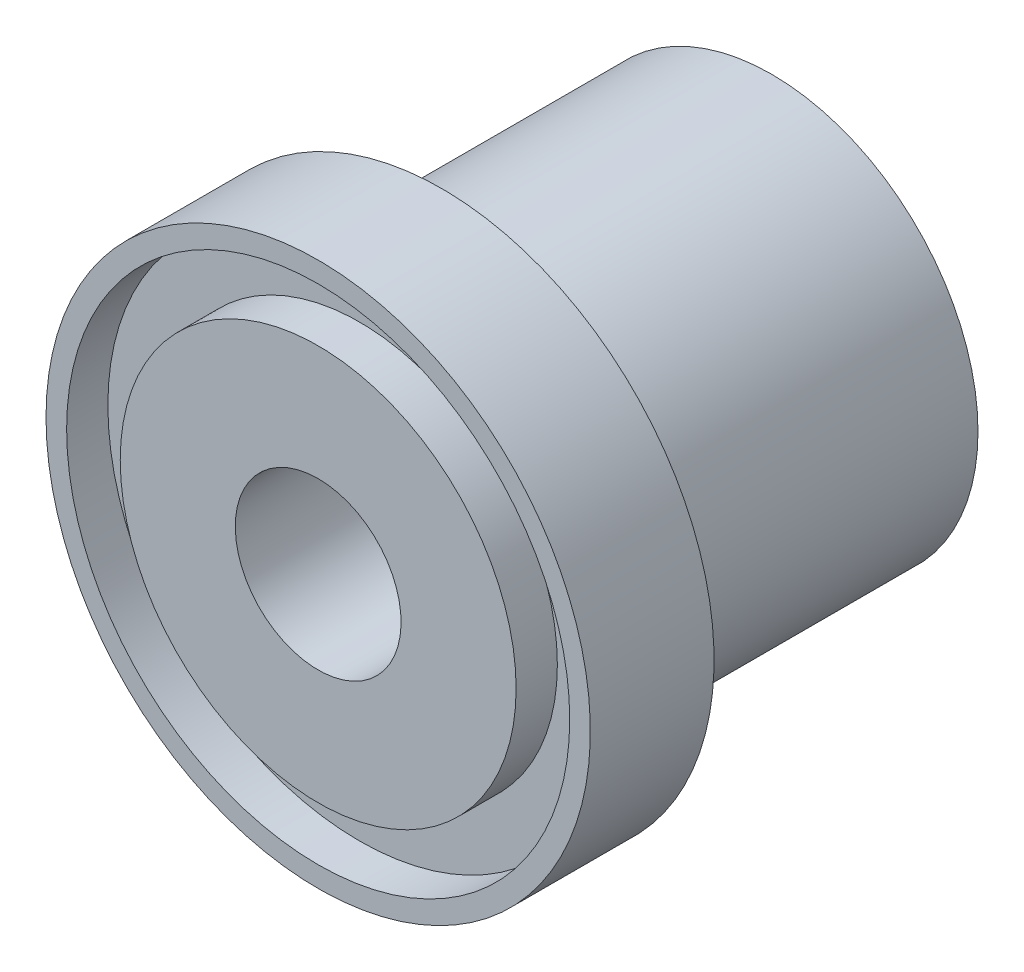
SolidWorks part; units mm, degrees
ref_plane "Front Plane" through (0, 0, 0) normal (0, 0, 1) x (1, 0, 0)
ref_plane "Top Plane" through (0, 0, 0) normal (0, 1, 0) x (1, 0, 0)
ref_plane "Right Plane" through (0, 0, 0) normal (1, 0, 0) x (0, 0, -1)
sketch "Sketch1" plane through (0, 0, 0) normal (0, 0, 1) x (1, 0, 0)
  circle A0 centre (43.1743, 8.5503) radius 6.35
  dimension "D2" = 12.7
extrude "Boss-Extrude1" add sketch "Sketch1" against normal up to surface (10.16 mm away)
sketch "Sketch3" plane through (0, 0, 0) normal (0, 0, 1) x (1, 0, 0)
  circle A0 centre (43.1743, 8.5503) radius 8.382
  dimension "D1" = 16.764
extrude "Boss-Extrude2" add sketch "Sketch3" along normal blind 3.81
sketch "Sketch5" plane through (0, 0, -10.16) normal (0, 0, -1) x (-1, 0, 0)
  circle A0 centre (-43.1743, 8.5503) radius 2.5527
extrude "Cut-Extrude2" cut sketch "Sketch5" against normal through all
sketch "Sketch6" plane through (0, 0, 3.81) normal (0, 0, 1) x (1, 0, 0)
  circle A0 centre (43.1743, 8.5503) radius 7.747
  circle A1 centre (43.1743, 8.5503) radius 6.096
  dimension "D1" = 15.494
  dimension "D2" = 12.192
extrude "Cut-Extrude3" cut sketch "Sketch6" against normal blind 1.27
